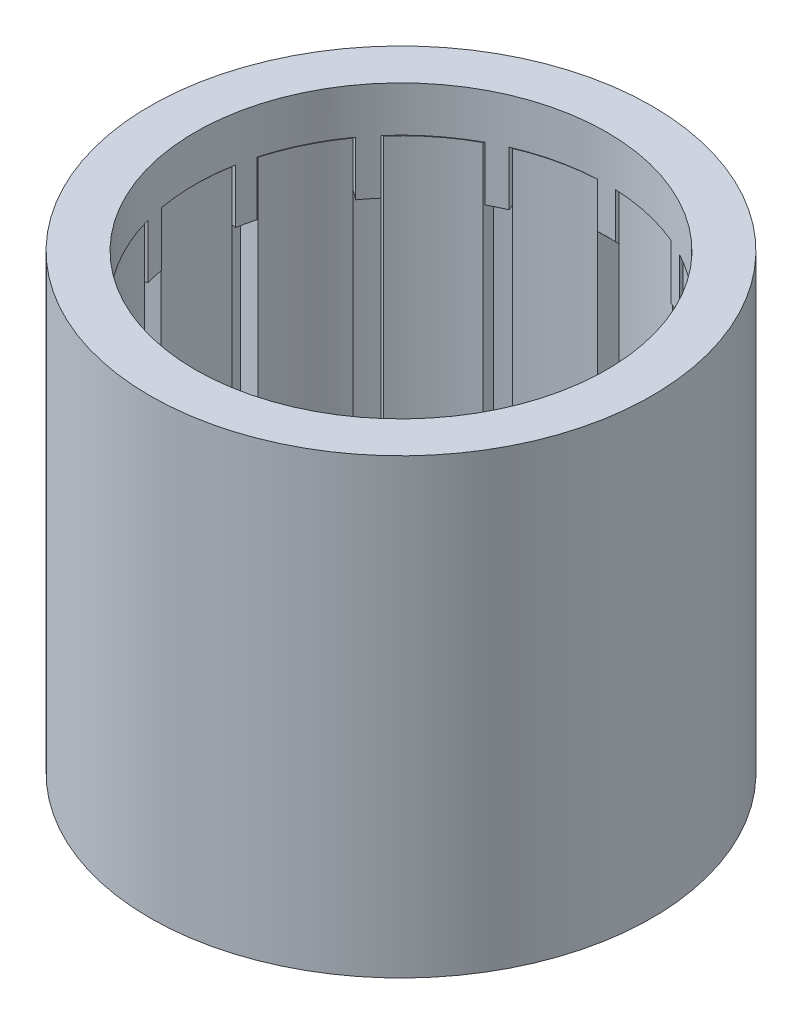
SolidWorks part; units mm, degrees
material "6061-T6 (SS)"
ref_plane "Front Plane" through (0, 0, 0) normal (0, 0, 1) x (1, 0, 0)
ref_plane "Top Plane" through (0, 0, 0) normal (0, 1, 0) x (1, 0, 0)
ref_plane "Right Plane" through (0, 0, 0) normal (1, 0, 0) x (0, 0, -1)
sketch "Sketch2" plane through (0, 0, 0) normal (1, 0, 0) x (0, 0, -1)
  line L0 (0, 0) -> (0, 12.2143) construction
  line L1 (12.975, 0) -> (13.875, 0)
  line L2 (13.875, 0) -> (13.875, 25)
  line L3 (13.875, 25) -> (11.375, 25)
  line L4 (11.375, 25) -> (11.375, 22.5)
  line L5 (11.375, 22.5) -> (12.975, 22.5)
  line L6 (12.975, 22.5) -> (12.975, 0)
  dimension "D1" = 0.9
  dimension "D2" = 25
  dimension "D3" = 27.75
  dimension "D4" = 22.5
  dimension "D5" = 2.5
revolve "Revolve1" add sketch "Sketch2" angle 360 about L0
sketch "Sketch3" plane through (0, 22.5, 0) normal (0, -1, 0) x (1, 0, 0)
  line L0 (0.5, -11.364) -> (0.5703, -12.9625)
  line L1 (-0.5, -11.364) -> (-0.5703, -12.9625)
  arc A0 (-0.5, -11.364) -> (0.5, -11.364) centre (0, 0) ccw
  circle A1 centre (0, 0) radius 11.375 construction
  circle A2 centre (0, 0) radius 12.975 construction
  arc A3 (-0.5703, -12.9625) -> (0.5703, -12.9625) centre (0, 0) ccw
  point P11 (0, -11.375)
  dimension "D1" = 1
extrude "Boss-Extrude1" add sketch "Sketch3" along normal offset from surface (3 mm away) 19.5 up to face at (0, 0, -13.875)
chamfer "Chamfer1" distance 0.5 angle 45 1 edges at (0, 19.5, -11.375)
pattern_circular "CirPattern1" count 14 over 360 about axis through (0, 0, 0) along (0, -1, 0) of "Boss-Extrude1"
sketch "Sketch4" plane through (0, 22.5, 0) normal (0, -1, 0) x (1, 0, 0)
  line L4 (-6.1787, -11.2956) -> (-5.5163, -10.0621)
  line L5 (-8.5823, -7.6171) -> (-9.6375, -8.5372)
  line L6 (-6.1787, -11.2956) -> (-5.5163, -10.0621)
  line L7 (-8.5823, -7.6171) -> (-9.6375, -8.5372)
  arc A4 (-9.6375, -8.5372) -> (-6.1787, -11.2956) centre (0, 0) ccw
  arc A5 (-8.5823, -7.6171) -> (-5.5163, -10.0621) centre (0, 0) ccw
  arc A6 (-9.6375, -8.5372) -> (-6.1787, -11.2956) centre (0, 0) ccw
  arc A7 (-8.5823, -7.6171) -> (-5.5163, -10.0621) centre (0, 0) ccw
  dimension "D1" = 0.1
extrude "Boss-Extrude2" add sketch "Sketch4" along normal offset from surface (21.9 mm away) 0.5 from offset 0.1 separate body up to face at (0, 0, -13.875)
pattern_circular "CirPattern2" count 14 over 360 about axis through (0, 0, 0) along (0, -1, 0) of bodies 104
